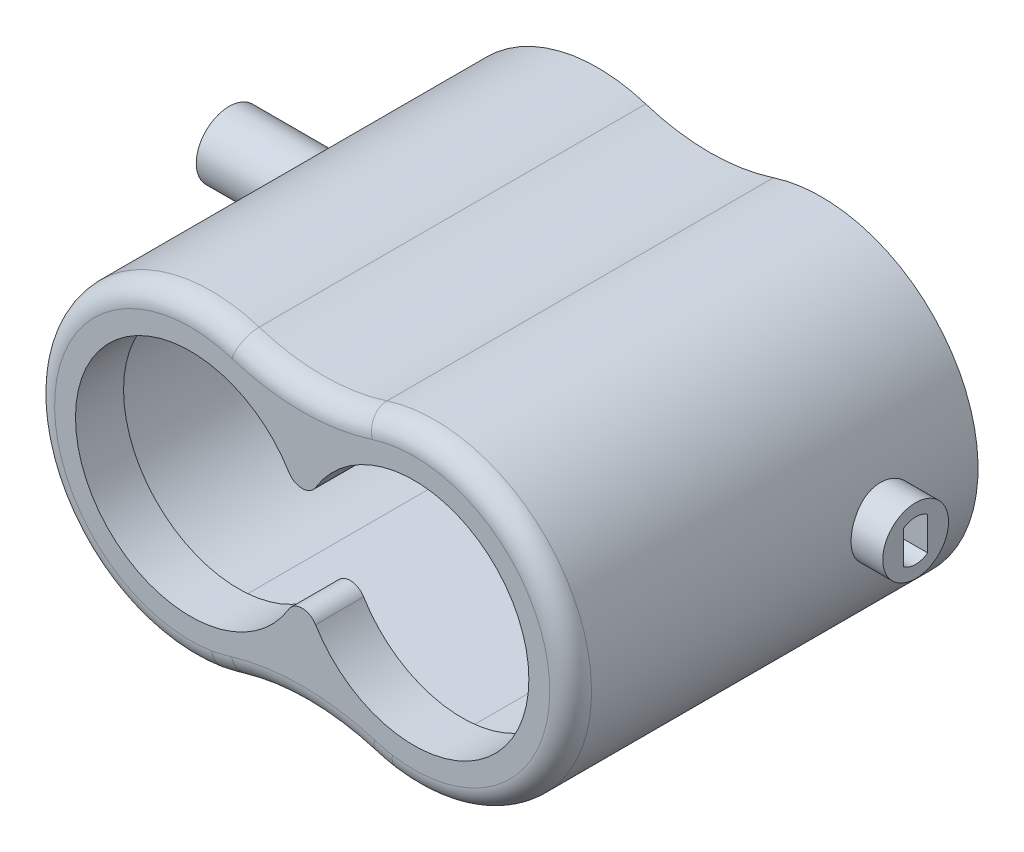
SolidWorks part; units mm, degrees
ref_plane "Front Plane" through (0, 0, 0) normal (0, 0, 1) x (1, 0, 0)
ref_plane "Top Plane" through (0, 0, 0) normal (0, 1, 0) x (1, 0, 0)
ref_plane "Right Plane" through (0, 0, 0) normal (1, 0, 0) x (0, 0, -1)
sketch "Sketch3" plane through (0, 0, 0) normal (0, 0, 1) x (1, 0, 0)
  line L0 (27.94, 0) -> (-27.94, 0)
  line L1 (10.541, 26.0769) -> (10.541, 5.842) construction
  line L2 (25.4, 5.842) -> (9.525, 5.842)
  line L3 (-27.94, 0) -> (-27.94, 3.302)
  line L4 (0, 0) -> (0, 36.6745) construction
  line L5 (-25.4, 5.842) -> (-9.525, 5.842)
  line L6 (3.175, 12.192) -> (3.175, 19.8087)
  line L7 (27.94, 0) -> (27.94, 3.302)
  line L8 (-3.175, 12.192) -> (-3.175, 19.8087)
  arc A0 (9.525, 5.842) -> (3.175, 12.192) centre (9.525, 12.192) cw
  arc A1 (-9.525, 5.842) -> (-3.175, 12.192) centre (-9.525, 12.192) ccw
  arc A6 (-27.94, 3.302) -> (-25.4, 5.842) centre (-25.4, 3.302) cw
  arc A7 (7.7651, 63.0194) -> (10.541, 26.0769) centre (13.589, 44.8815) cw
  arc A8 (-1.6307, 52.1036) -> (-1.6307, 37.6593) centre (-13.589, 44.8815) ccw
  arc A9 (-10.541, 26.0769) -> (-3.175, 19.8087) centre (-9.525, 19.8087) cw
  arc A10 (1.6307, 37.6593) -> (-1.6307, 37.6593) centre (0, 36.6745) ccw
  arc A11 (1.6307, 52.1036) -> (1.6307, 37.6593) centre (13.589, 44.8815) cw
  arc A12 (-7.7651, 63.0194) -> (-10.541, 26.0769) centre (-13.589, 44.8815) ccw
  arc A13 (27.94, 3.302) -> (25.4, 5.842) centre (25.4, 3.302) ccw
  arc A17 (10.541, 26.0769) -> (3.175, 19.8087) centre (9.525, 19.8087) ccw
  arc A18 (-7.7651, 63.0194) -> (7.7651, 63.0194) centre (0, 87.2034) ccw
  arc A19 (1.6307, 52.1036) -> (-1.6307, 52.1036) centre (0, 53.0885) cw
  point P52 (-20.9726, 27.3206)
  point P60 (20.9726, 27.3206)
  dimension "D1" = 6.35
  dimension "D4" = 6.35
  dimension "D5" = 1.905
extrude "Boss-Extrude1" add sketch "Sketch3" along normal blind 8.89
ref_plane "Plane1" through (0, 0, 0) normal (0, 0, -1) x (-1, 0, 0)
sketch "Sketch5" plane through (0, 0, 0) normal (0, 0, -1) x (-1, 0, 0)
  line L2 (13.7795, 60.1215) -> (-13.7795, 60.1215)
  line L4 (13.7795, 29.6415) -> (-13.7795, 29.6415)
  arc A0 (-13.7795, 60.1215) -> (-13.7795, 29.6415) centre (-13.7795, 44.8815) ccw
  arc A1 (13.7795, 60.1215) -> (13.7795, 29.6415) centre (13.7795, 44.8815) cw
  point P2 (0, 57.3846)
  point P4 (0, 32.3783)
  point P10 (0, 60.1215)
extrude "Cut-Extrude1" cut sketch "Sketch5" against normal blind 3.048
ref_plane "Plane2" through (0, 0, 3.048) normal (0, 0, -1) x (-1, 0, 0)
sketch "Sketch8" plane through (0, 0, 3.048) normal (0, 0, -1) x (-1, 0, 0)
  line L0 (0, 44.8815) -> (0, 56.0575) construction
  line L1 (0, 44.8815) -> (-27.559, 44.8815) construction
  line L2 (0, 44.8815) -> (27.559, 44.8815) construction
  line L3 (0, 44.8815) -> (0, 33.7055) construction
  arc A0 (-1.6307, 52.1036) -> (-1.6307, 37.6593) centre (-13.589, 44.8815) ccw construction
  arc A1 (1.6307, 37.6593) -> (1.6307, 52.1036) centre (13.589, 44.8815) ccw construction
  point P14 (0, 56.0575)
  point P15 (0, 33.7055)
hole_wizard "#4-40 Tapped Hole1" positions "Sketch12" profile "Sketch11" tap size "#4-40" standard "ANSI Inch"
sketch "Sketch12" plane through (0, 0, 3.048) normal (0, 0, -1) x (-1, 0, 0)
  point P0 (0, 56.0575)
  point P3 (0, 33.7055)
sketch "Sketch11" plane through (0, 56.0575, 3.048) normal (1, 0, 0) x (0, 1, 0)
  line L0 (0, 0) -> (0, 4.9972)
  line L1 (0, 4.9972) -> (1.1303, 4.318)
  line L2 (1.1303, 4.318) -> (1.1303, 0)
  line L5 (1.1303, 0) -> (0, 0)
  line L10 (0, 4.9972) -> (-1.1303, 4.318) construction
  line L11 (0, -6.35) -> (0, 107.95) construction
  dimension "Tap Drill Dia." = 2.2606
  dimension "Tap Drill Depth" = 4.318
  dimension "Drill Angle" = 118
cosmetic thread "Hole Thread3" parameters "D1"=4.318, "D2"=2.8448
cosmetic thread "Hole Thread4" parameters "D1"=4.318, "D2"=2.8448
ref_plane "Plane3" through (0, 0, 0) normal (0, -1, 0) x (-1, 0, 0)
sketch "Sketch14" plane through (0, 0, 0) normal (0, -1, 0) x (-1, 0, 0)
  line L0 (0, 0) -> (0, -8.89) construction
  line L1 (27.94, -8.89) -> (-27.94, -8.89) construction
  line L2 (0, -4.445) -> (22.225, -4.445) construction
  line L3 (0, -4.445) -> (-22.225, -4.445) construction
  circle A0 centre (22.225, -4.445) radius 1.8288
  circle A1 centre (-22.225, -4.445) radius 1.8288
extrude "Cut-Extrude2" cut sketch "Sketch14" against normal up to next
sketch "Sketch15" plane through (0, 0, 8.89) normal (0, 0, 1) x (1, 0, 0)
  line L0 (-10.541, 26.0769) -> (-57.743, 0)
  line L1 (-57.743, 0) -> (-18.6994, -16.511)
  line L2 (-18.6994, -16.511) -> (69.2386, -8.2555)
  line L3 (69.2386, -8.2555) -> (10.541, 26.0769)
  arc A0 (-10.541, 26.0769) -> (-7.8842, 26.7321) centre (-16.744, 56.9445) ccw
  arc A1 (-7.8842, 26.7321) -> (8.0849, 26.6749) centre (0.0041, -0.1674) cw
  arc A2 (8.0849, 26.6749) -> (10.541, 26.0769) centre (14.8855, 49.2645) ccw
  arc A3 (10.541, 26.0769) -> (7.7651, 63.0194) centre (13.589, 44.8815) ccw construction
extrude "Cut-Extrude3" cut sketch "Sketch15" against normal blind 38.862
sketch "Sketch19" plane through (0, 0, 0) normal (0, 0, -1) x (-1, 0, 0)
  line L0 (-13.7795, 29.6415) -> (13.7795, 29.6415) construction
  line L1 (-13.7795, 29.6415) -> (13.7795, 29.6415)
  line L2 (-13.7795, 60.1215) -> (13.7795, 60.1215)
  arc A0 (13.7795, 29.6415) -> (13.7795, 60.1215) centre (13.7795, 44.8815) ccw
  arc A1 (13.7795, 29.6415) -> (13.7795, 60.1215) centre (13.7795, 44.8815) ccw construction
  arc A2 (-13.7795, 29.6415) -> (-13.7795, 60.1215) centre (-13.7795, 44.8815) cw
  arc A3 (-7.7651, 63.0194) -> (7.7651, 63.0194) centre (0, 87.2034) ccw
  arc A4 (-7.7651, 63.0194) -> (-10.541, 26.0769) centre (-13.589, 44.8815) ccw
  arc A5 (10.541, 26.0769) -> (7.7651, 63.0194) centre (13.589, 44.8815) ccw
  arc A6 (7.8842, 26.7321) -> (10.541, 26.0769) centre (16.744, 56.9445) ccw
  arc A7 (-10.541, 26.0769) -> (-8.0849, 26.6749) centre (-14.8855, 49.2645) ccw
  arc A8 (-8.0849, 26.6749) -> (7.8842, 26.7321) centre (-0.0041, -0.1674) cw
extrude "Boss-Extrude3" add sketch "Sketch19" along normal blind 40.64
sketch "Sketch20" plane through (0, 0, 0) normal (1, 0, 0) x (0, 0, -1)
  line L0 (40.64, 25.8315) -> (40.64, 63.9315) construction
  line L1 (-8.89, 63.9315) -> (-8.89, 25.8315) construction
  circle A0 centre (29.21, 44.8815) radius 4
  point P5 (40.64, 44.8815)
  dimension "D1" = 8
  dimension "D2" = 38.1
extrude "Boss-Extrude4" add sketch "Sketch20" along normal blind 6 from offset 30.48 separate body
extrude "Boss-Extrude5" add sketch "Sketch20<2>" along normal blind 0.508 and the other way blind 6 from offset 30.48 offset against normal yes
sketch "Sketch20<2>" plane through (0, 0, 0) normal (1, 0, 0) x (0, 0, -1) same geometry as "Sketch20"
sketch "Sketch21" plane through (36.48, 0, 0) normal (1, 0, 0) x (0, 0, -1)
  circle A0 centre (29.21, 44.8815) radius 2.5
  circle A1 centre (29.21, 44.8815) radius 4 construction
  dimension "D1" = 5
extrude "Cut-Extrude5" cut sketch "Sketch21" against normal blind 24.678 from offset 55.88 offset against normal yes
sketch "Sketch22" plane through (36.48, 0, 0) normal (1, 0, 0) x (0, 0, -1)
  line L0 (27.745, 46.9073) -> (27.745, 42.8557)
  line L1 (30.675, 46.9073) -> (30.675, 42.8557)
  arc A0 (27.745, 46.9073) -> (30.675, 46.9073) centre (29.21, 44.8815) cw
  arc A1 (27.745, 42.8557) -> (30.675, 42.8557) centre (29.21, 44.8815) ccw
  circle A2 centre (29.21, 44.8815) radius 4 construction
  dimension "D2" = 2.5
  dimension "D1" = 2.93
extrude "Cut-Extrude6" cut sketch "Sketch22" against normal blind 6
sketch "Sketch23" plane through (-36.48, 0, 0) normal (-1, 0, 0) x (0, 0, 1)
  circle A0 centre (-29.21, 44.8815) radius 4.75
  circle A1 centre (-29.21, 44.8815) radius 3.5963
  dimension "D1" = 9.5
extrude "Boss-Extrude6" add sketch "Sketch23" against normal blind 3.984 from offset 2.794 offset against normal yes
sketch "Sketch25" plane through (-36.48, 0, 0) normal (-1, 0, 0) x (0, 0, 1)
  circle A0 centre (-29.21, 44.8815) radius 2.5
  circle A1 centre (-29.21, 44.8815) radius 4
  circle A2 centre (-29.21, 44.8815) radius 2.5 construction
  circle A3 centre (-29.21, 44.8815) radius 4 construction
extrude "Boss-Extrude7" add sketch "Sketch25" along normal blind 10.5
sketch "Sketch26" plane through (-33.686, 0, 0) normal (-1, 0, 0) x (0, 0, 1)
  circle A0 centre (-29.21, 44.8815) radius 2.5
  circle A1 centre (-29.21, 44.8815) radius 2.5 construction
  circle A2 centre (-29.21, 44.8815) radius 4.725
sketch "Sketch27" plane through (0, 0, -40.64) normal (0, 0, -1) x (-1, 0, 0)
  line L0 (46.98, 40.8815) -> (46.98, 48.8815) construction
  line L1 (33.686, 40.8815) -> (46.98, 40.8815) construction
  circle A0 centre (43.98, 44.8815) radius 1
  dimension "D1" = 2
  dimension "D2" = 3
  dimension "D3" = 4
extrude "Cut-Extrude7" cut sketch "Sketch27" against normal blind 9.666
fillet "Fillet6" radius 2.54 6 edges at (-32.5854, 46.3089, 8.89) (-9.2055, 26.3756, 8.89) (9.3049, 26.343, 8.89) (0.1045, 27.8647, 8.89) (32.5854, 46.3089, 8.89) (0, 61.8034, 8.89)
